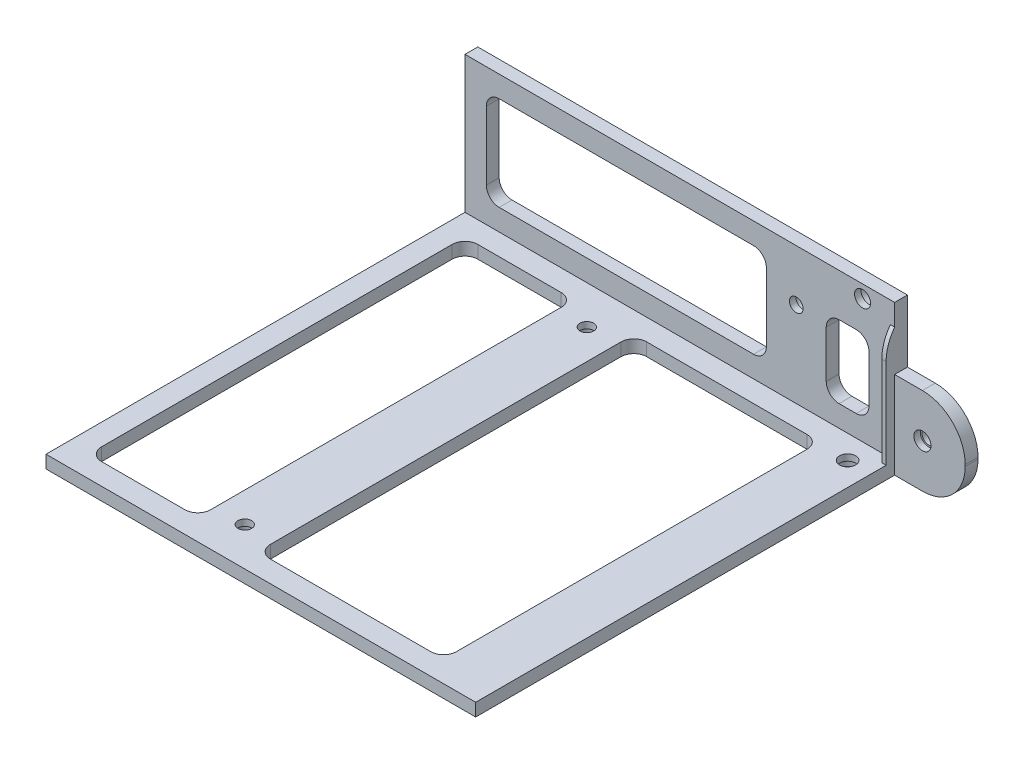
SolidWorks part; units mm, degrees
note: The reader was unsure of these and kept them because the rebuilt part matched: shared geometry of "Sketch1<4>", "Sketch1<5>".
ref_plane "Front Plane" through (0, 0, 0) normal (0, 0, 1) x (1, 0, 0)
ref_plane "Top Plane" through (0, 0, 0) normal (0, 1, 0) x (1, 0, 0)
ref_plane "Right Plane" through (0, 0, 0) normal (1, 0, 0) x (0, 0, -1)
sketch "Sketch1" plane through (0, 0, 0) normal (0, 0, 1) x (1, 0, 0)
  line L1 (0, 0) -> (117, 0)
  line L2 (0, 0) -> (0, 35)
  line L3 (0, 35) -> (117, 35)
  line L4 (117, 0) -> (117, 35)
  line L5 (0, 0) -> (117, 0)
  line L6 (0, 0) -> (0, 3)
  line L7 (0, 3) -> (117, 3)
  line L8 (117, 0) -> (117, 3)
  line L9 (99.5, 30) -> (100.5, 30)
  line L10 (99.5, 30) -> (99.5, 3)
  line L11 (99.5, 3) -> (100.5, 3)
  line L12 (100.5, 30) -> (100.5, 3)
  circle A0 centre (77.5, 23) radius 1.6
  circle A1 centre (93, 32) radius 1.875
  circle A2 centre (107, 10.2) radius 1.6
  dimension "D3" = 3.75
  dimension "D4" = 3.2
  dimension "D13" = 3.2
  dimension "D1" = 35
  dimension "D2" = 117
  dimension "D5" = 23
  dimension "D6" = 32
  dimension "D7" = 3
  dimension "D8" = 1
  dimension "D9" = 99.5
  dimension "D10" = 22
  dimension "D11" = 6.5
  dimension "D12" = 5
  dimension "D14" = 10
  dimension "D15" = 10.2
extrude "Boss-Extrude1" add sketch "Sketch1" along normal blind 3 contours L10 L3 L2 L7 A1 A0 | L3 L12 L7 L4 | L7 L2 L1 L4
extrude "Boss-Extrude2" add sketch "Sketch1<4>" along normal blind 101 contours L7 L2 L1 L4
sketch "Sketch1<4>" plane through (0, 0, 0) normal (0, 0, 1) x (1, 0, 0) same geometry as "Sketch1"
extrude "Boss-Extrude3" add sketch "Sketch1<5>" along normal blind 5 contours L10 L11 L12 L9
sketch "Sketch1<5>" plane through (0, 0, 0) normal (0, 0, 1) x (1, 0, 0) same geometry as "Sketch1"
sketch "Sketch2" plane through (0, 0, 3) normal (0, 0, 1) x (1, 0, 0)
  line L0 (100.5, 30) -> (100.5, 3) construction
  line L1 (117, 35) -> (100.5, 35)
  line L2 (117, 35) -> (117, 20.4)
  line L3 (117, 20.4) -> (100.5, 20.4)
  line L4 (100.5, 35) -> (100.5, 20.4)
  circle A0 centre (107, 10.2) radius 1.6 construction
  dimension "D1" = 10.2
extrude "Cut-Extrude1" cut sketch "Sketch2" against normal blind 5
sketch "Sketch3" plane through (0, 3, 0) normal (0, 1, 0) x (1, 0, 0)
  line L1 (117, -101) -> (100.5, -101)
  line L2 (117, -101) -> (117, -3)
  line L3 (117, -3) -> (100.5, -3)
  line L4 (100.5, -101) -> (100.5, -3)
extrude "Cut-Extrude2" cut sketch "Sketch3" against normal blind 5
fillet "Fillet1" radius 10 1 edges at (117, 20.4, 1.5)
fillet "Fillet2" radius 10 1 edges at (117, 0, 1.5)
sketch "Sketch4" plane through (0, 3, 0) normal (0, 1, 0) x (1, 0, 0)
  line L0 (99.5, -3) -> (0, -3) construction
  line L1 (100.5, -5) -> (100.5, -101) construction
  circle A0 centre (37.5, -12) radius 1.6
  circle A1 centre (37.5, -92) radius 1.6
  circle A2 centre (95, -8.5) radius 1.875
  dimension "D1" = 3.2
  dimension "D2" = 3.2
  dimension "D7" = 3.75
  dimension "D3" = 9
  dimension "D4" = 63
  dimension "D5" = 63
  dimension "D6" = 80
  dimension "D8" = 5.5
  dimension "D9" = 5.5
extrude "Cut-Extrude3" cut sketch "Sketch4" against normal blind 5
fillet "Fillet3" radius 10 1 edges at (100, 30, 5)
sketch "Sketch5" plane through (0, 0, 0) normal (0, -1, 0) x (1, 0, 0)
  circle A0 centre (37.5, 92) radius 2
  circle A1 centre (37.5, 12) radius 2
  circle A2 centre (95, 8.5) radius 2.5
  dimension "D1" = 4
  dimension "D2" = 4
  dimension "D3" = 5
extrude "Cut-Extrude4" cut sketch "Sketch5" against normal blind 1.5
sketch "Sketch6" plane through (0, 0, 3) normal (0, 0, 1) x (1, 0, 0)
  circle A0 centre (107, 10.2) radius 2
  dimension "D1" = 4
extrude "Cut-Extrude5" cut sketch "Sketch6" against normal blind 1.5
sketch "Sketch7" plane through (0, 0, 0) normal (0, 0, -1) x (-1, 0, 0)
  circle A0 centre (-77.5, 23) radius 2
  circle A1 centre (-93, 32) radius 2.25
  dimension "D1" = 4.5
  dimension "D2" = 4
extrude "Cut-Extrude6" cut sketch "Sketch7" against normal blind 1.5
sketch "Sketch8" plane through (0, 3, 0) normal (0, 1, 0) x (1, 0, 0)
  line L0 (99.5, -3) -> (0, -3) construction
  line L1 (5, -8) -> (30.5, -8)
  line L2 (5, -8) -> (5, -96)
  line L3 (5, -96) -> (30.5, -96)
  line L4 (30.5, -8) -> (30.5, -96)
  line L5 (44.5, -8) -> (88, -8)
  line L6 (44.5, -8) -> (44.5, -96)
  line L7 (44.5, -96) -> (88, -96)
  line L8 (88, -8) -> (88, -96)
  line L9 (0, -101) -> (100.5, -101) construction
  line L10 (0, -101) -> (0, -3) construction
  circle A0 centre (95, -8.5) radius 1.875 construction
  circle A1 centre (37.5, -12) radius 1.6 construction
  dimension "D1" = 7
  dimension "D2" = 7
  dimension "D3" = 5
  dimension "D4" = 5
  dimension "D5" = 5
  dimension "D6" = 5
  dimension "D7" = 5
  dimension "D8" = 7
extrude "Cut-Extrude7" cut sketch "Sketch8" against normal blind 10
fillet "Fillet4" radius 3 8 edges at (44.5, 1.5, 8) (88, 1.5, 8) (88, 1.5, 96) (44.5, 1.5, 96) (5, 1.5, 96) (30.5, 1.5, 96) (30.5, 1.5, 8) (5, 1.5, 8)
sketch "Sketch9" plane through (0, 0, 3) normal (0, 0, 1) x (1, 0, 0)
  line L0 (99.5, 3) -> (0, 3) construction
  line L1 (5, 30) -> (70.5, 30)
  line L2 (5, 30) -> (5, 8)
  line L3 (5, 8) -> (70.5, 8)
  line L4 (70.5, 30) -> (70.5, 8)
  line L5 (84.5, 25) -> (94.5, 25)
  line L6 (84.5, 25) -> (84.5, 8)
  line L7 (84.5, 8) -> (94.5, 8)
  line L8 (94.5, 25) -> (94.5, 8)
  line L9 (0, 3) -> (0, 35) construction
  line L10 (0, 35) -> (100.5, 35) construction
  line L11 (99.5, 30) -> (99.5, 3) construction
  circle A0 centre (77.5, 23) radius 1.6 construction
  circle A1 centre (93, 32) radius 1.875 construction
  dimension "D6" = 7
  dimension "D1" = 5
  dimension "D2" = 5
  dimension "D3" = 5
  dimension "D4" = 7
  dimension "D5" = 7
  dimension "D7" = 5
  dimension "D8" = 5
extrude "Cut-Extrude8" cut sketch "Sketch9" against normal blind 10
fillet "Fillet5" radius 3 8 edges at (84.5, 25, 1.5) (84.5, 8, 1.5) (94.5, 8, 1.5) (94.5, 25, 1.5) (5, 8, 1.5) (70.5, 8, 1.5) (70.5, 30, 1.5) (5, 30, 1.5)
